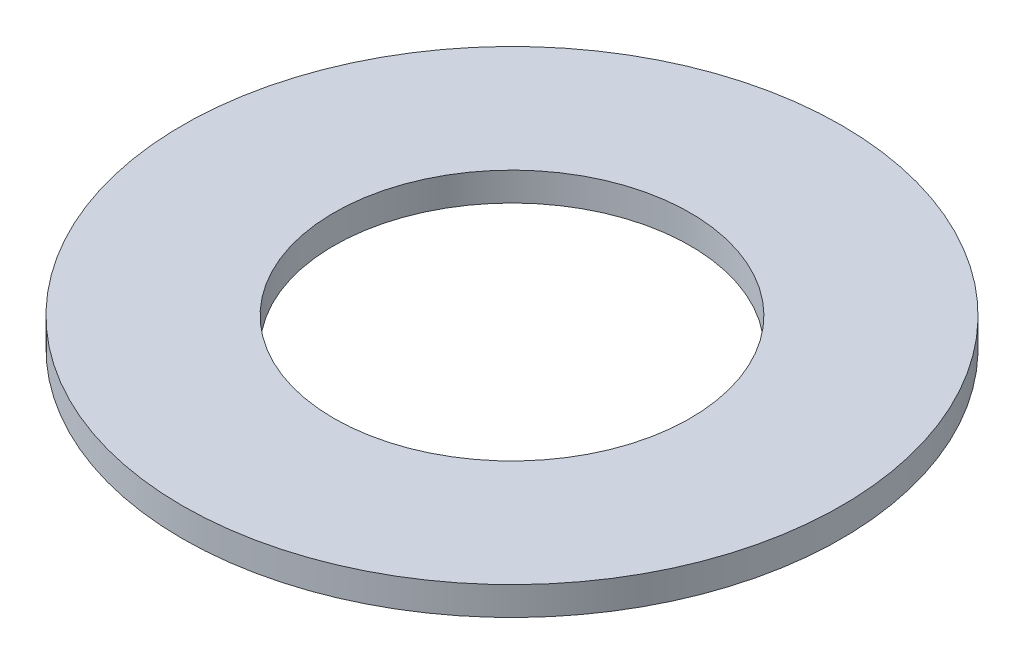
SolidWorks part; units mm, degrees
ref_plane "Front Plane" through (0, 0, 0) normal (0, 0, 1) x (1, 0, 0)
ref_plane "Top Plane" through (0, 0, 0) normal (0, 1, 0) x (1, 0, 0)
ref_plane "Right Plane" through (0, 0, 0) normal (1, 0, 0) x (0, 0, -1)
sketch "Sketch1" plane through (0, 0, 0) normal (0, 1, 0) x (1, 0, 0)
  circle A0 centre (0, 0) radius 92.5
  dimension "FLANGE_OD" = 185
extrude "Boss-Extrude1" add sketch "Sketch1" along normal blind 8
sketch "Sketch2" plane through (0, 0, 0) normal (0, 1, 0) x (1, 0, 0)
  circle A0 centre (0, 0) radius 50
  dimension "BORE_D" = 100
extrude "Cut-Extrude1" cut sketch "Sketch2" along normal through all
sketch "Sketch3" plane through (0, 8, 0) normal (0, 1, 0) x (1, 0, 0)
  circle A0 centre (0, 0) radius 41.3607 construction
  circle A1 centre (-41.3607, 0) radius 4.6151
  dimension "BOLT_D" = 9.2302
  dimension "BOLT_PCD" = 82.7215
extrude "Cut-Extrude2" cut sketch "Sketch3" against normal blind 5.1218 rebuild error yes
pattern_circular "CirPattern1" count 6 over 360 rebuild error yes
